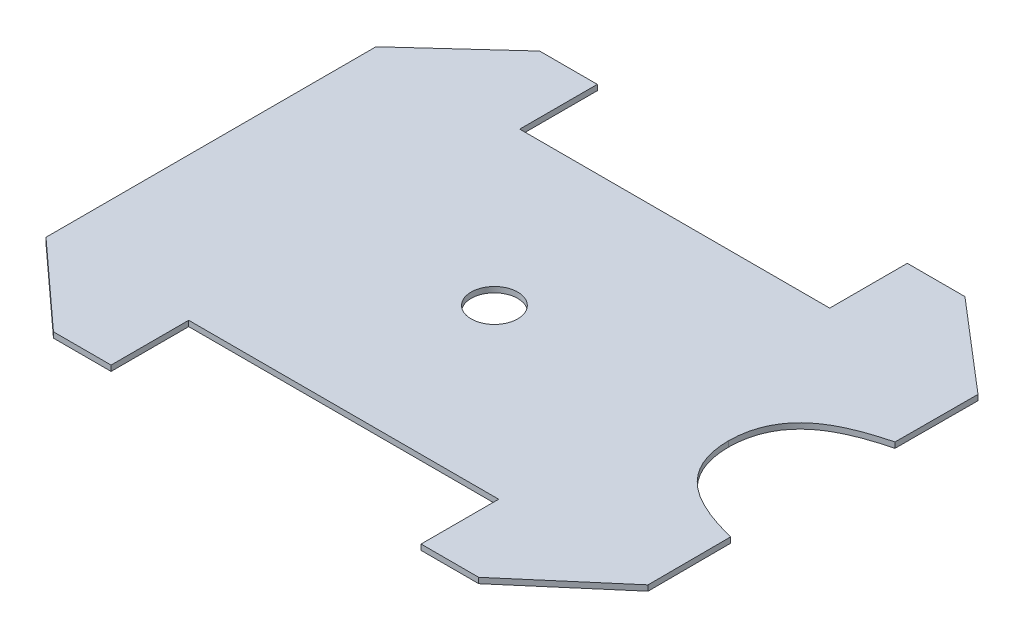
SolidWorks part; units mm, degrees
ref_plane "Спереди" through (0, 0, 0) normal (0, 0, 1) x (1, 0, 0)
ref_plane "Сверху" through (0, 0, 0) normal (0, 1, 0) x (1, 0, 0)
ref_plane "Справа" through (0, 0, 0) normal (1, 0, 0) x (0, 0, -1)
sketch "Эскиз1" plane through (0, 0, 0) normal (0, 1, 0) x (1, 0, 0)
  line L1 (-269.7922, 74.6607) -> (-269.7922, -223.012)
  line L2 (139.0683, -293.4928) -> (191.0683, -293.4928)
  line L3 (-140.5865, 145.1415) -> (-192.5865, 145.1415)
  line L4 (139.0683, -223.4928) -> (139.0683, -293.4928)
  line L5 (139.0683, 145.1415) -> (191.0683, 145.1415)
  line L6 (-140.5865, 75.1415) -> (-140.5865, 145.1415)
  line L7 (-0.7591, -12.2026) -> (-0.7591, 227.1905) construction
  line L8 (273.3416, 74.6607) -> (273.1017, 0.0307)
  line L9 (-140.5865, -223.4928) -> (139.0683, -223.4928)
  line L10 (139.0683, 75.1415) -> (139.0683, 145.1415)
  line L11 (-140.5865, 75.1415) -> (139.0683, 75.1415)
  line L12 (-140.5865, -223.4928) -> (-140.5865, -293.4928)
  line L13 (-140.5865, -293.4928) -> (-192.5865, -293.4928)
  line L14 (273.3416, -223.012) -> (273.1017, -148.382)
  line L17 (-326.8393, -74.1757) -> (107.7018, -74.1757) construction
  line L22 (-269.7922, 74.6607) -> (-192.5865, 145.1415)
  line L23 (-269.7922, -223.012) -> (-192.5865, -293.4928)
  line L24 (-263.7922, 74.6607) -> (-387.0064, 74.6607) construction
  line L25 (-269.7922, -223.012) -> (-392.2998, -223.012) construction
  line L26 (273.3416, -223.012) -> (191.0683, -293.4928)
  line L27 (273.3416, 74.6607) -> (191.0683, 145.1415)
  spline S0 degree 3 poles (273.1017, 0.0307) (239.4366, -8.8528) (197.437, -23.6267) (197.0474, -74.1757) knots 0 0 0 0 1 1 1 1
  spline S1 degree 3 poles (241.3333, -15.1188) (241.3449, -11.9635) (241.3327, -4.2402) (241.3148, -3.4392) knots 0 0 0 0 1 1 1 1 weights 1 0.504087 0.504087 1 construction
  spline S2 degree 3 poles (273.1017, -148.382) (239.4366, -139.4985) (197.437, -124.7247) (197.0474, -74.1757) knots 0 0 0 0 1 1 1 1
extrude "Вытянуть1" add sketch "Эскиз1" along normal blind 5
sketch "Эскиз2" plane through (0, 5, 0) normal (0, 1, 0) x (-1, 0, 0)
  circle A0 centre (14.23, 74.0267) radius 21
extrude "Вырез-Вытянуть1" cut sketch "Эскиз2" against normal through all
